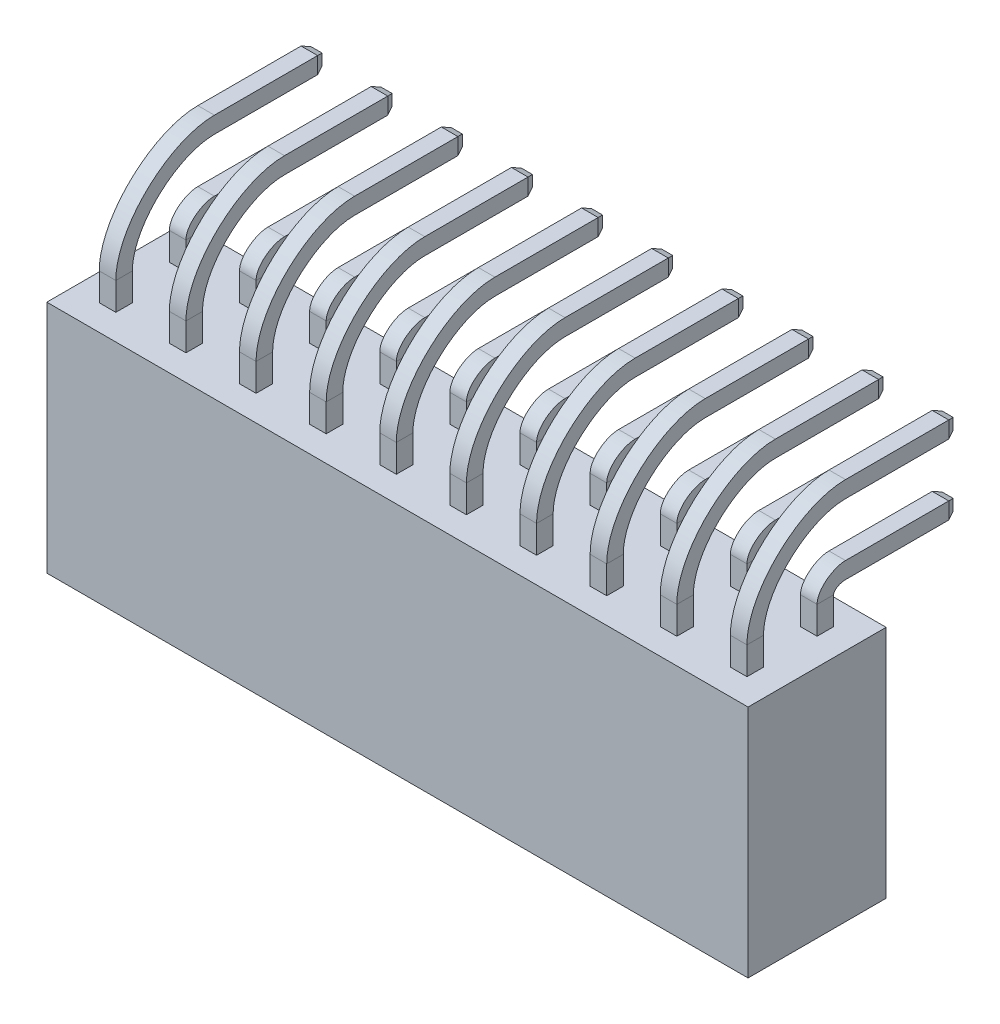
SolidWorks part; units mm, degrees
other "Детальный элемент1"
ref_plane "Спереди" through (0, 0, 0) normal (0, 0, 1) x (1, 0, 0)
ref_plane "Сверху" through (0, 0, 0) normal (0, 1, 0) x (1, 0, 0)
ref_plane "Справа" through (0, 0, 0) normal (1, 0, 0) x (0, 0, -1)
sketch "Эскиз1" plane through (0, 0, 0) normal (0, 0, 1) x (1, 0, 0)
  line L1 (-12.7, -11.33) -> (12.7, -11.33)
  line L2 (-12.7, -11.33) -> (-12.7, -2.83)
  line L3 (-12.7, -2.83) -> (12.7, -2.83)
  line L4 (12.7, -11.33) -> (12.7, -2.83)
  line L5 (-12.7, -11.33) -> (12.7, -2.83) construction
  line L6 (-12.7, -2.83) -> (12.7, -11.33) construction
  point P0 (0, -7.08)
  dimension "D1" = 8.5
  dimension "D2" = 11.33
  dimension "D3" = 25.4
extrude "Бобышка-Вытянуть1" add sketch "Эскиз1" along normal blind 5
sketch "Эскиз2" plane through (0, -11.33, 0) normal (0, -1, 0) x (1, 0, 0)
  line L0 (-12.7, 5) -> (12.7, 5) construction
  line L1 (11.005, 1.655) -> (11.855, 1.655)
  line L2 (11.005, 1.655) -> (11.005, 0.805)
  line L3 (11.005, 0.805) -> (11.855, 0.805)
  line L4 (11.855, 1.655) -> (11.855, 0.805)
  line L5 (11.005, 1.655) -> (11.855, 0.805) construction
  line L6 (11.005, 0.805) -> (11.855, 1.655) construction
  line L7 (11.005, 4.195) -> (11.855, 4.195)
  line L8 (11.005, 4.195) -> (11.005, 3.345)
  line L9 (11.005, 3.345) -> (11.855, 3.345)
  line L10 (11.855, 4.195) -> (11.855, 3.345)
  line L11 (11.005, 4.195) -> (11.855, 3.345) construction
  line L12 (11.005, 3.345) -> (11.855, 4.195) construction
  line L13 (12.7, 5) -> (12.7, 0) construction
  point P0 (11.43, 1.23)
  point P5 (11.43, 3.77)
  point P13 (0, 0)
  point P16 (0, 0)
  point P17 (0, 0)
  point P18 (0, 0)
  dimension "D1" = 2.54
  dimension "D2" = 0.85
  dimension "D3" = 1.23
  dimension "D4" = 1.27
extrude "Вырез-Вытянуть1" cut sketch "Эскиз2" against normal blind 6
chamfer "Фаска3" distance 0.6 angle 39 8 edges at (11.855, -11.33, 1.23) (11.43, -11.33, 0.805) (11.005, -11.33, 1.23) (11.43, -11.33, 1.655) (11.855, -11.33, 3.77) (11.43, -11.33, 3.345) (11.005, -11.33, 3.77) (11.43, -11.33, 4.195) first distance on face at (11.43, -11.33, 1.23)
pattern_linear "Линейный массив1" count 10 spacing 2.54 along (-1, 0, 0) of "Фаска3", "Вырез-Вытянуть1"
sketch "Эскиз3" plane through (0, -2.83, 0) normal (0, 1, 0) x (1, 0, 0)
  line L1 (11.13, -4.07) -> (11.73, -4.07)
  line L2 (11.13, -4.07) -> (11.13, -3.47)
  line L3 (11.13, -3.47) -> (11.73, -3.47)
  line L4 (11.73, -4.07) -> (11.73, -3.47)
  line L5 (11.13, -4.07) -> (11.73, -3.47) construction
  line L6 (11.13, -3.47) -> (11.73, -4.07) construction
  line L7 (11.73, -1.53) -> (11.13, -1.53)
  line L8 (11.73, -1.53) -> (11.73, -0.93)
  line L9 (11.73, -0.93) -> (11.13, -0.93)
  line L10 (11.13, -1.53) -> (11.13, -0.93)
  line L11 (11.73, -1.53) -> (11.13, -0.93) construction
  line L12 (11.73, -0.93) -> (11.13, -1.53) construction
  point P0 (11.43, -3.77)
  point P5 (11.43, -1.23)
  point P13 (0, 0)
  point P15 (0, 0)
  dimension "D1" = 0.6
extrude "Бобышка-Вытянуть2" add sketch "Эскиз3" along normal blind 1 separate body
sketch "Эскиз4" plane through (0, 0, 0) normal (0, 0, 1) x (1, 0, 0)
  line L1 (11.13, -1.57) -> (11.73, -1.57)
  line L2 (11.13, -1.57) -> (11.13, -0.97)
  line L3 (11.13, -0.97) -> (11.73, -0.97)
  line L4 (11.73, -1.57) -> (11.73, -0.97)
  line L5 (11.13, -1.57) -> (11.73, -0.97) construction
  line L6 (11.13, -0.97) -> (11.73, -1.57) construction
  line L7 (11.13, 0.97) -> (11.73, 0.97)
  line L8 (11.13, 0.97) -> (11.13, 1.57)
  line L9 (11.13, 1.57) -> (11.73, 1.57)
  line L10 (11.73, 0.97) -> (11.73, 1.57)
  line L11 (11.13, 0.97) -> (11.73, 1.57) construction
  line L12 (11.13, 1.57) -> (11.73, 0.97) construction
  point P0 (11.43, -1.27)
  point P5 (11.43, 1.27)
  point P11 (0, 0)
  dimension "D1" = 0.6
  dimension "D2" = 1.27
  dimension "D3" = 2.54
extrude "Бобышка-Вытянуть3" add sketch "Эскиз4" along normal blind 0.5 and the other way blind 3.5 separate body
loft "По сечениям1" add section face at (11.43, -1.27, 0.5) section face at (11.43, -1.83, 1.23) start constraint normal to profile start tangent length 1 end constraint normal to profile end tangent length 1 connector at (11.13, -1.57, 0.5) connector at (11.13, -1.83, 0.93)
loft "По сечениям2" add section face at (11.43, 1.27, 0.5) section face at (11.43, -1.83, 3.77) start constraint normal to profile start tangent length 1 end constraint normal to profile end tangent length 1 connector at (11.13, 0.97, 0.5) connector at (11.13, -1.83, 3.47)
chamfer "Фаска1" distance 0.1 angle 69 4 edges at (11.43, -1.57, -3.5) (11.13, -1.27, -3.5) (11.43, -0.97, -3.5) (11.73, -1.27, -3.5) first distance on face at (11.43, -1.27, -3.5)
chamfer "Фаска2" distance 0.1 angle 69 4 edges at (11.43, 0.97, -3.5) (11.13, 1.27, -3.5) (11.73, 1.27, -3.5) (11.43, 1.57, -3.5) first distance on face at (11.43, 1.27, -3.5)
pattern_linear "Линейный массив2" count 10 spacing 2.54 along (-1, 0, 0) of bodies 112 113 114 109
equation "\"N\"= 20"
equation "\"D3@Эскиз1\"=\"N\"/2*2.54"
equation "\"D1@Линейный массив1\"=\"N\"/2"
equation "\"D1@Линейный массив2\"=\"N\"/2"
